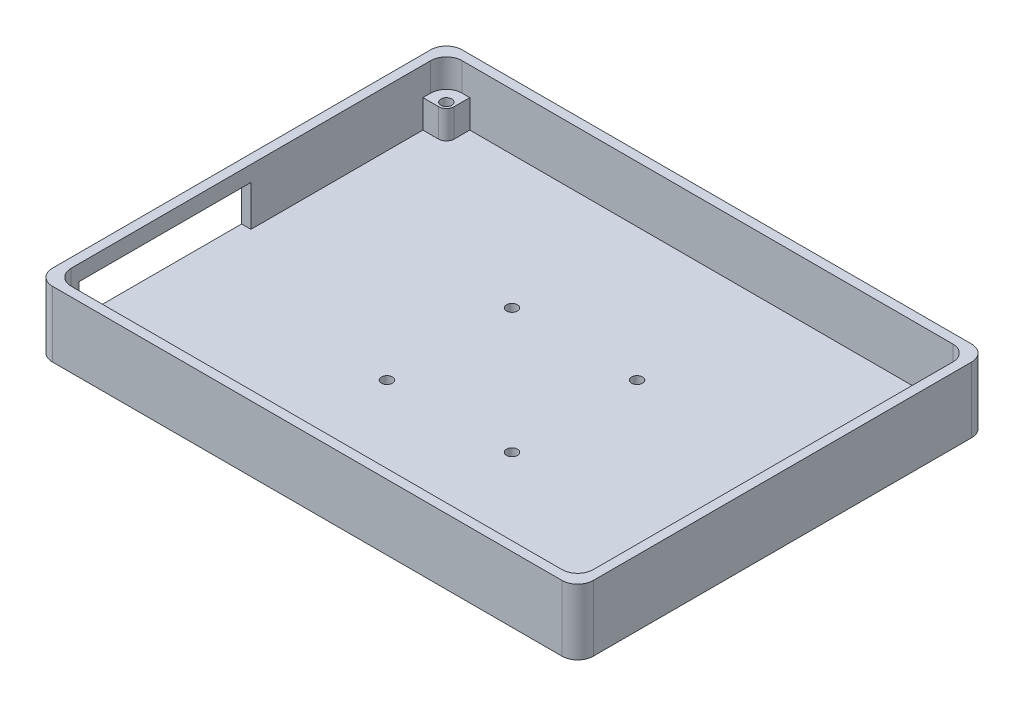
SolidWorks part; units mm, degrees
note: The reader was unsure of these and kept them because the rebuilt part matched: shared geometry of "草图1<3>", "草图1<5>".
ref_plane "前视基准面" through (0, 0, 0) normal (0, 0, 1) x (1, 0, 0)
ref_plane "上视基准面" through (0, 0, 0) normal (0, 1, 0) x (1, 0, 0)
ref_plane "右视基准面" through (0, 0, 0) normal (1, 0, 0) x (0, 0, -1)
other "Configuration Table"
sketch "草图1" plane through (0, 0, 0) normal (0, 1, 0) x (1, 0, 0)
  line L0 (0, 0) -> (78.5, 0)
  line L1 (0, 0) -> (-78.5, 0)
  line L2 (-78.5, 0) -> (-78.5, -115)
  line L3 (78.5, 0) -> (78.5, -115)
  line L4 (-78.5, -115) -> (78.5, -115)
  line L5 (-78.5, 0) -> (-78.5, 5)
  line L6 (-78.5, 5) -> (78.5, 5)
  line L7 (78.5, 5) -> (83.5, 5)
  line L8 (83.5, 5) -> (83.5, -115)
  line L9 (83.5, -115) -> (83.5, -120)
  line L10 (83.5, -120) -> (-83.5, -120)
  line L11 (-83.5, -120) -> (-83.5, 5)
  line L12 (-83.5, 5) -> (-78.5, 5)
  line L13 (-83.5, -120) -> (-86.5, -120)
  line L14 (-83.5, -120) -> (-83.5, -123)
  line L15 (-83.5, -123) -> (83.5, -123)
  line L16 (83.5, -123) -> (86.5, -123)
  line L17 (86.5, -123) -> (86.5, 8)
  line L18 (86.5, 8) -> (-86.5, 8)
  line L19 (-86.5, 8) -> (-86.5, -123)
  line L20 (-86.5, -123) -> (-83.5, -123)
  line L21 (-78.5, -2.5) -> (-83.5, -2.5)
  line L22 (-76, 0) -> (-76, 5)
  line L23 (78.5, -2.5) -> (83.5, -2.5)
  line L24 (76, 0) -> (76, 5)
  line L25 (78.5, -112.5) -> (83.5, -112.5)
  line L26 (76, -115) -> (76, -120)
  line L27 (-76, -115) -> (-76, -120)
  line L28 (-78.5, -112.5) -> (-83.5, -112.5)
  line L29 (-76, 5) -> (-83.5, 5)
  line L30 (-83.5, -2.5) -> (-83.5, 5)
  line L31 (76, 5) -> (83.5, 5)
  line L32 (83.5, -2.5) -> (83.5, 5)
  line L33 (83.5, -112.5) -> (83.5, -120)
  line L34 (76, -120) -> (83.5, -120)
  line L35 (-76, -120) -> (-83.5, -120)
  line L36 (-83.5, -112.5) -> (-83.5, -120)
  circle A0 centre (78.5, 0) radius 1.75
  circle A1 centre (-78.5, 0) radius 1.75
  circle A2 centre (-78.5, -115) radius 1.75
  circle A3 centre (78.5, -115) radius 1.75
  circle A4 centre (78.5, 0) radius 2.5
  circle A5 centre (-78.5, 0) radius 2.5
  circle A6 centre (-78.5, -115) radius 2.5
  circle A7 centre (78.5, -115) radius 2.5
  dimension "D1" = 3.5
  dimension "D2" = 3.5
  dimension "D3" = 3.5
  dimension "D7" = 3.5
  dimension "D4" = 78.5
  dimension "D5" = 115
  dimension "D6" = 78.5
  dimension "D8" = 5
  dimension "D9" = 157
  dimension "D10" = 120
  dimension "D11" = 5
  dimension "D12" = 5
  dimension "D13" = 167
  dimension "D14" = 3
  dimension "D15" = 3
  dimension "D16" = 131
  dimension "D17" = 173
extrude "凸台-拉伸1" add sketch "草图1" along normal blind 3
extrude "凸台-拉伸2" add sketch "草图1<3>" along normal blind 21 contours L18 L19 L13 L11 L12 L6 L7 L8 L9 L10 L14 L15 L16 L17 | L19 L20 L14 L13
sketch "草图1<3>" plane through (0, 0, 0) normal (0, 1, 0) x (1, 0, 0) same geometry as "草图1"
extrude "凸台-拉伸3" add sketch "草图1<5>" along normal blind 12 contours L4 A7 L3 A3 | L3 A7 L4 A3 | L4 A6 L2 A2 | L2 A6 L4 A2 | L1 A5 L5 A1 | L5 A5 L2 A1 | L2 A5 L1 A1 | L3 A4 L0 A0 | L0 A4 L3 A0 | A5 L5 L12 L11 L21 | A5 L22 L6 L5 | A4 L23 L8 L7 L6 L24 | A7 L26 L10 L9 L8 L25 | A6 L28 L11 L10 L27
sketch "草图1<5>" plane through (0, 0, 0) normal (0, 1, 0) x (1, 0, 0) same geometry as "草图1"
sketch "草图3" plane through (-86.5, 0, 0) normal (-1, 0, 0) x (0, 0, 1)
  line L0 (57.5, 21) -> (112.5, 21)
  line L1 (-8, 21) -> (123, 21) construction
  line L2 (112.5, 21) -> (112.5, 0)
  line L3 (-8, 0) -> (123, 0) construction
  line L4 (112.5, 0) -> (57.5, 0)
  line L5 (57.5, 0) -> (57.5, 21)
  line L6 (57.5, 0) -> (57.5, 3)
  line L7 (57.5, 3) -> (112.5, 3)
  line L8 (57.5, 21) -> (57.5, 16)
  line L9 (57.5, 16) -> (112.5, 16)
  dimension "D1" = 5
  dimension "D2" = 3
  dimension "D3" = 55
extrude "切除-拉伸1" cut sketch "草图3" against normal blind 4 contours L9 L5 L7 L2
sketch "草图4" plane through (0, 12, 0) normal (0, 1, 0) x (1, 0, 0)
  circle A0 centre (-78.5, 0) radius 1.75
  circle A1 centre (78.5, 0) radius 1.75
  circle A2 centre (78.5, -115) radius 1.75
  circle A3 centre (-78.5, -115) radius 1.75
extrude "切除-拉伸2" cut sketch "草图4" against normal blind 14
sketch "草图5" plane through (0, 3, 0) normal (0, 1, 0) x (1, 0, 0)
  line L0 (-83.5, -57.5) -> (83.5, -57.5)
  line L1 (-83.5, -120) -> (-83.5, 5) construction
  line L2 (83.5, 5) -> (83.5, -120) construction
  line L3 (83.5, -57.5) -> (108.3452, -66.6209)
  line L4 (108.3452, -66.6209) -> (108.5295, -66.9894)
  line L5 (0, 5) -> (0, -120)
  line L6 (-83.5, 5) -> (83.5, 5) construction
  line L7 (83.5, -120) -> (-83.5, -120) construction
  line L8 (0, -57.5) -> (20, -57.5)
  line L9 (20, -57.5) -> (20, -37.5)
  line L10 (20, -37.5) -> (-20, -37.5)
  line L11 (-20, -37.5) -> (-20, -77.5)
  line L12 (-20, -77.5) -> (20, -77.5)
  line L13 (20, -77.5) -> (20, -57.5)
  circle A0 centre (-20, -37.5) radius 1.75
  circle A1 centre (20, -37.5) radius 1.75
  circle A2 centre (20, -77.5) radius 1.75
  circle A3 centre (-20, -77.5) radius 1.75
extrude "切除-拉伸3" cut sketch "草图5" against normal blind 4 contours L9 A1 L10 | L10 A1 L9 | L12 A2 L13 | L13 A2 L12 | L11 A3 L12 | L12 A3 L11 | L11 A0 L10 | L10 A0 L11
fillet "圆角1" radius 5 4 edges at (-86.5, 10.5, -8) (-86.5, 10.5, 123) (86.5, 10.5, -8) (86.5, 10.5, 123)
fillet "圆角2" radius 5 4 edges at (-83.5, 16.5, 120) (83.5, 16.5, 120) (83.5, 16.5, -5) (-83.5, 16.5, -5)
